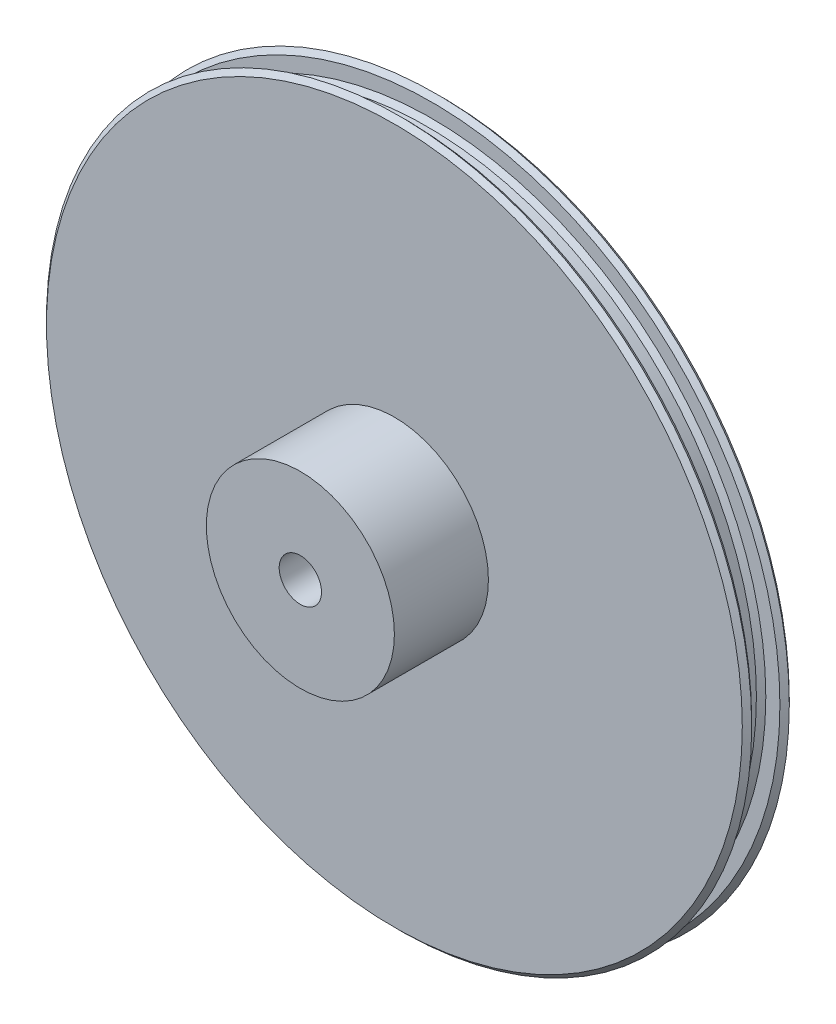
SolidWorks part; units mm, degrees
ref_plane "Front Plane" through (0, 0, 0) normal (0, 0, 1) x (1, 0, 0)
ref_plane "Top Plane" through (0, 0, 0) normal (0, 1, 0) x (1, 0, 0)
ref_plane "Right Plane" through (0, 0, 0) normal (1, 0, 0) x (0, 0, -1)
sketch "Sketch1" plane through (0, 0, 0) normal (0, 0, 1) x (1, 0, 0)
  circle A0 centre (0, 0) radius 75
extrude "Boss-Extrude1" add sketch "Sketch1" along normal blind 2
sketch "Sketch2" plane through (0, 0, 2) normal (0, 0, 1) x (1, 0, 0)
  circle A0 centre (0, 0) radius 70
extrude "Boss-Extrude2" add sketch "Sketch2" along normal blind 6
sketch "Sketch3" plane through (0, 0, 8) normal (0, 0, 1) x (1, 0, 0)
  circle A0 centre (0, 0) radius 75
extrude "Boss-Extrude3" add sketch "Sketch3" along normal blind 2
chamfer "Chamfer1" distance 1 3 edges at (75, 0, 0) (75, 0, 2) (70, 0, 2)
chamfer "Chamfer2" distance 1 3 edges at (75, 0, 10) (75, 0, 8) (70, 0, 8)
sketch "Sketch4" plane through (0, 0, 10) normal (0, 0, 1) x (1, 0, 0)
  circle A0 centre (0, 0) radius 20
  dimension "D1" = 40
extrude "Boss-Extrude5" add sketch "Sketch4" along normal blind 20
sketch "Sketch5" plane through (0, 0, 30) normal (0, 0, 1) x (1, 0, 0)
  circle A0 centre (0, 0) radius 4.5
extrude "Cut-Extrude1" cut sketch "Sketch5" against normal through all
sketch "Sketch6" plane through (0, 0, 30) normal (0, 0, 1) x (1, 0, 0)
  line L1 (-1.5, 7.5) -> (1.5, 7.5)
  line L2 (-1.5, 7.5) -> (-1.5, 1.5)
  line L3 (-1.5, 1.5) -> (1.5, 1.5)
  line L4 (1.5, 7.5) -> (1.5, 1.5)
  line L5 (-1.5, 7.5) -> (1.5, 1.5) construction
  line L6 (-1.5, 1.5) -> (1.5, 7.5) construction
  circle A0 centre (0, 0) radius 4.5 construction
  point P0 (0, 4.5)
  dimension "D1" = 6
  dimension "D2" = 3
extrude "Cut-Extrude2" cut sketch "Sketch6" against normal blind 20 from offset 5 offset against normal yes
